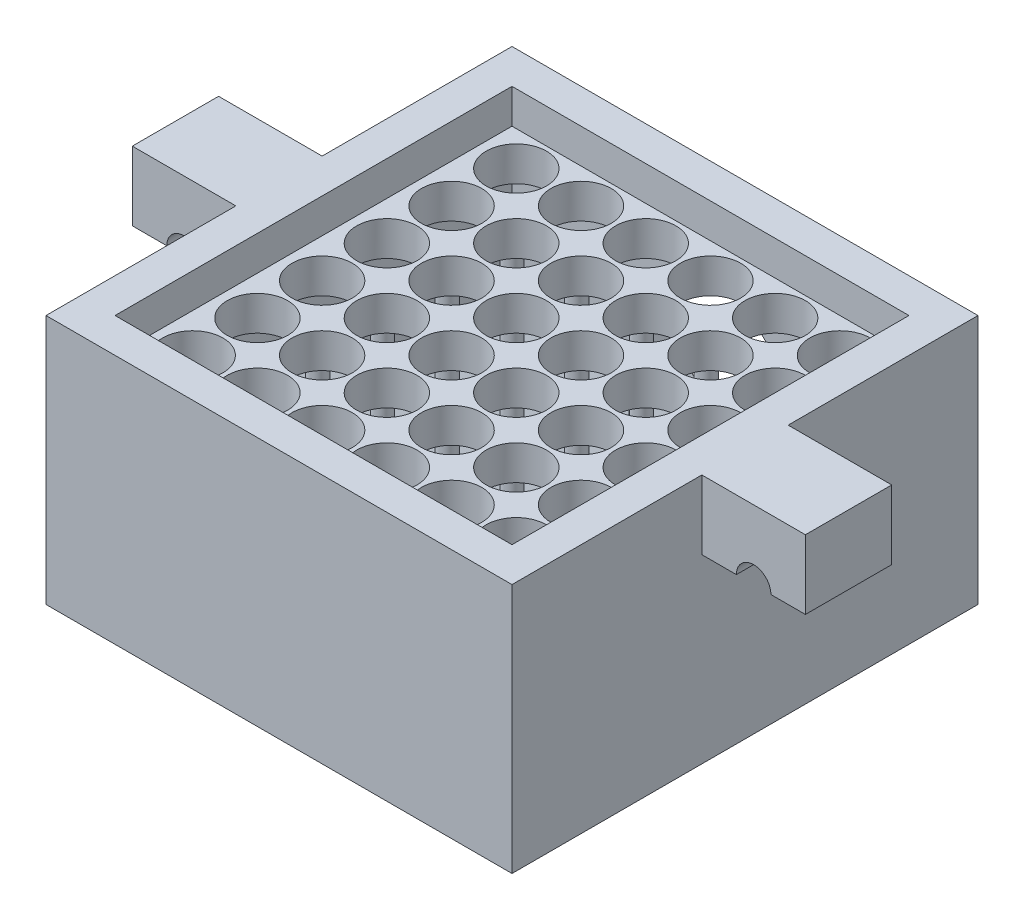
SolidWorks part; units mm, degrees
note: '?' marks a value the reader was unsure of.
ref_plane "Front Plane" through (0, 0, 0) normal (0, 0, 1) x (1, 0, 0)
ref_plane "Top Plane" through (0, 0, 0) normal (0, 1, 0) x (1, 0, 0)
ref_plane "Right Plane" through (0, 0, 0) normal (1, 0, 0) x (0, 0, -1)
sketch "Sketch1" plane through (0, 0, 0) normal (0, 1, 0) x (1, 0, 0)
  line L0 (-13.5, 13.5) -> (13.5, 13.5)
  line L1 (-11.5, -11.5) -> (11.5, -11.5)
  line L2 (-11.5, -11.5) -> (-11.5, 11.5)
  line L3 (-11.5, 11.5) -> (11.5, 11.5)
  line L4 (11.5, -11.5) -> (11.5, 11.5)
  line L5 (-11.5, -11.5) -> (11.5, 11.5) construction
  line L6 (-11.5, 11.5) -> (11.5, -11.5) construction
  line L7 (13.5, -13.5) -> (13.5, 13.5)
  line L8 (-13.5, -13.5) -> (13.5, -13.5)
  line L9 (-13.5, -13.5) -> (-13.5, 13.5)
  point P0 (0, 0)
  dimension "D1" = 23
  dimension "D2" = 2
extrude "Boss-Extrude1" add sketch "Sketch1" along normal blind 2
sketch "Sketch2" plane through (0, 0, 0) normal (0, -1, 0) x (1, 0, 0)
  line L1 (-13.5, 13.5) -> (13.5, 13.5)
  line L2 (-13.5, 13.5) -> (-13.5, -13.5)
  line L3 (-13.5, -13.5) -> (13.5, -13.5)
  line L4 (13.5, 13.5) -> (13.5, -13.5)
  line L5 (-13.5, 13.5) -> (13.5, -13.5) construction
  line L6 (-13.5, -13.5) -> (13.5, 13.5) construction
  point P0 (0, 0)
extrude "Boss-Extrude2" add sketch "Sketch2" along normal blind 2
sketch "Sketch12" plane through (-13.5, 0, 0) normal (-1, 0, 0) x (0, 0, 1)
  line L0 (-13.5, 2) -> (13.5, 2) construction
  line L1 (-2.5, -2) -> (2.5, -2)
  line L2 (-2.5, -2) -> (-2.5, 2)
  line L3 (-2.5, 2) -> (2.5, 2)
  line L4 (2.5, -2) -> (2.5, 2)
  line L5 (-2.5, -2) -> (2.5, 2) construction
  line L6 (-2.5, 2) -> (2.5, -2) construction
  point P0 (0, 0)
  dimension "D1" = 5
extrude "Boss-Extrude9" add sketch "Sketch12" along normal blind 6
ref_axis "Axis2" through (0, 0, 0) along (0, -1, 0)?
ref_plane "Plane1" through (0, 0, 0) normal (1, 0, 0) x (0, 0, -1)
mirror "Mirror1" about plane through (0, 0, 0) normal (1, 0, 0) of "Boss-Extrude9"
sketch "Sketch13" plane through (0, 0, 0) normal (0, 1, 0) x (1, 0, 0)
  line L0 (11.5, -11.5) -> (11.5, 11.5) construction
  line L1 (11.5, 11.5) -> (-11.5, 11.5) construction
  circle A0 centre (9.5, 9.5) radius 1.75
  dimension "D1" = 3.5
  dimension "D2" = 2
  dimension "D3" = 2
extrude "Cut-Extrude4" cut sketch "Sketch13" against normal up to next
pattern_linear "LPattern3" count 6 spacing 3.75 along (0, 0, 1) count 6 spacing 3.75 along (-1, 0, 0) of "Cut-Extrude4"
sketch "Sketch15" plane through (0, 0, 2.5) normal (0, 0, 1) x (1, 0, 0)
  line L0 (-19.5, -2) -> (-13.5, -2) construction
  line L1 (-17.5, -2) -> (-15.5, -2)
  line L2 (19.5, -2) -> (13.5, -2) construction
  line L3 (17.5, -2) -> (15.5, -2)
  arc A0 (-15.5, -2) -> (-17.5, -2) centre (-16.5, -2) ccw
  arc A1 (17.5, -2) -> (15.5, -2) centre (16.5, -2) ccw
  dimension "D1" = 1
  dimension "D2" = 1
extrude "Cut-Extrude5" cut sketch "Sketch15" against normal up to next
sketch "Sketch14" plane through (0, -2, 0) normal (0, -1, 0) x (1, 0, 0)
  line L0 (11.5, -11.5) -> (11.5, 11.5)
  line L1 (-13.5, -13.5) -> (13.5, -13.5)
  line L2 (-13.5, -13.5) -> (-13.5, 13.5)
  line L3 (-13.5, 13.5) -> (13.5, 13.5)
  line L4 (13.5, -13.5) -> (13.5, 13.5)
  line L5 (-13.5, -13.5) -> (13.5, 13.5) construction
  line L6 (-13.5, 13.5) -> (13.5, -13.5) construction
  line L7 (-11.5, 11.5) -> (11.5, 11.5)
  line L8 (-11.5, -11.5) -> (-11.5, 11.5)
  line L9 (-11.5, -11.5) -> (11.5, -11.5)
  point P0 (0, 0)
  dimension "D1" = 2
extrude "Boss-Extrude10" add sketch "Sketch14" along normal blind 8.5
sketch "Sketch16" plane through (11.5, 0, 0) normal (-1, 0, 0) x (0, 0, 1)
  line L0 (11.5, -10.5) -> (-11.5, -10.5)
  line L1 (-11.5, -10.5) -> (-11.5, -9.5)
  line L2 (11.5, -10.5) -> (11.5, -2) construction
  line L3 (11.5, -3) -> (11.5, -10.5)
  line L4 (-11.5, -10.5) -> (-11.5, -2) construction
  line L5 (-11.5, -9.5) -> (11.5, -3)
  dimension "D1" = 7.5
  dimension "D2" = 1
extrude "Boss-Extrude11" add sketch "Sketch16" along normal up to surface (23 mm away) up to face at (-11.5, -6.25, 0)
sketch "Sketch17" plane through (0, 0, -13.5) normal (0, 0, -1) x (-1, 0, 0)
  line L1 (-13.5, -6.25) -> (13.5, -6.25) construction
  line L2 (-13.5, 2) -> (-13.5, -10.5) construction
  line L3 (13.5, 2) -> (13.5, -10.5) construction
  circle A0 centre (0, -6.25) radius 4.25
  dimension "D1" = 8.5
  dimension "D2" = 4.25
sketch "Sketch18" plane through (0, -10.5, 0) normal (0, -1, 0) x (1, 0, 0)
  line L1 (13.5, 13.5) -> (-13.5, 13.5)
  line L2 (13.5, 13.5) -> (13.5, -13.5)
  line L3 (13.5, -13.5) -> (-13.5, -13.5)
  line L4 (-13.5, 13.5) -> (-13.5, -13.5)
  line L5 (13.5, 13.5) -> (-13.5, -13.5) construction
  line L6 (13.5, -13.5) -> (-13.5, 13.5) construction
  point P0 (0, 0)
extrude "Boss-Extrude12" add sketch "Sketch18" along normal blind 2
extrude "Cut-Extrude10" cut sketch "Sketch17" against normal up to surface (2 mm away) up to face at (0, -5.75, -11.5)
sketch "Sketch19" plane through (0, -2, 0) normal (0, -1, 0) x (1, 0, 0)
  line L0 (11.5, 11.5) -> (-11.5, -11.5) construction
  line L1 (0, 0) -> (3.75, 0) construction
  line L2 (0, 0) -> (0, 3.75) construction
  line L3 (0, 3.75) -> (-3.75, 3.75) construction
  line L4 (3.75, 0) -> (3.75, 3.75) construction
  line L5 (3.75, 3.75) -> (7.5, 3.75) construction
  line L6 (7.5, 3.75) -> (7.5, 7.5) construction
  line L7 (7.5, 7.5) -> (3.75, 7.5) construction
  line L8 (3.75, 7.5) -> (0, 7.5) construction
  line L9 (0, 7.5) -> (-3.75, 7.5) construction
  line L10 (-3.75, 7.5) -> (-7.5, 7.5) construction
  line L11 (-7.5, 7.5) -> (-7.5, 3.75) construction
  line L12 (-7.5, 3.75) -> (-7.5, 0) construction
  line L13 (-7.5, 0) -> (-3.75, 0) construction
  line L14 (-3.75, 0) -> (-3.75, -3.75) construction
  line L15 (-3.75, -3.75) -> (-7.5, -3.75) construction
  line L16 (-7.5, -3.75) -> (-7.5, -7.5) construction
  line L17 (-7.5, -7.5) -> (-3.75, -7.5) construction
  line L18 (-3.75, -7.5) -> (0, -7.5) construction
  line L19 (0, -7.5) -> (0, -3.75) construction
  line L20 (0, -3.75) -> (3.75, -3.75) construction
  line L21 (3.75, -3.75) -> (3.75, -7.5) construction
  line L22 (3.75, -7.5) -> (7.5, -7.5) construction
  line L23 (7.5, -7.5) -> (7.5, -3.75) construction
  line L24 (7.5, -3.75) -> (7.5, 0) construction
  circle A0 centre (0, 0) radius 0.5
  circle A1 centre (3.75, 0) radius 0.5
  circle A2 centre (0, 3.75) radius 0.5
  circle A3 centre (-3.75, 3.75) radius 0.5
  circle A4 centre (3.75, 3.75) radius 0.5
  circle A5 centre (7.5, 3.75) radius 0.5
  circle A6 centre (7.5, 7.5) radius 0.5
  circle A7 centre (3.75, 7.5) radius 0.5
  circle A8 centre (0, 7.5) radius 0.5
  circle A9 centre (-3.75, 7.5) radius 0.5
  circle A10 centre (-7.5, 7.5) radius 0.5
  circle A11 centre (-7.5, 3.75) radius 0.5
  circle A12 centre (-7.5, 0) radius 0.5
  circle A13 centre (-3.75, 0) radius 0.5
  circle A14 centre (-3.75, -3.75) radius 0.5
  circle A15 centre (-7.5, -3.75) radius 0.5
  circle A16 centre (-7.5, -7.5) radius 0.5
  circle A17 centre (-3.75, -7.5) radius 0.5
  circle A18 centre (0, -7.5) radius 0.5
  circle A19 centre (0, -3.75) radius 0.5
  circle A20 centre (3.75, -3.75) radius 0.5
  circle A21 centre (3.75, -7.5) radius 0.5
  circle A22 centre (7.5, -7.5) radius 0.5
  circle A23 centre (7.5, -3.75) radius 0.5
  circle A24 centre (7.5, 0) radius 0.5
  dimension "D1" = 1
  dimension "D2" = 3.75
extrude "Boss-Extrude13" add sketch "Sketch19" along normal up to surface (4.3913 mm away)
